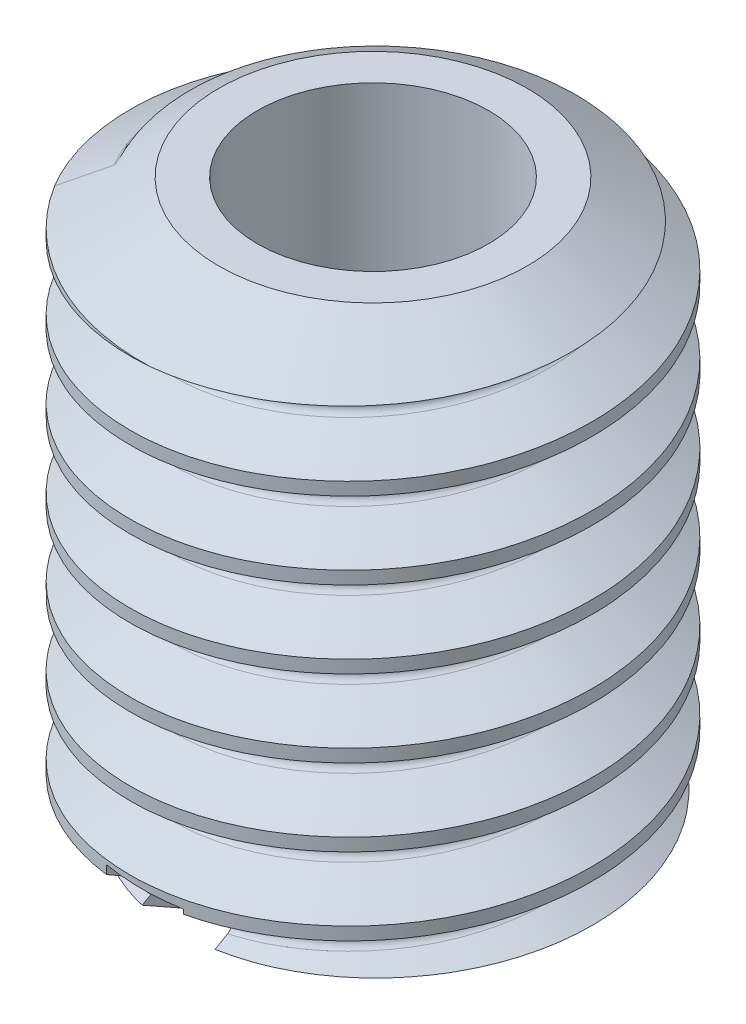
SolidWorks part; units mm, degrees
ref_plane "Front Plane" through (0, 0, 0) normal (0, 0, 1) x (1, 0, 0)
ref_plane "Top Plane" through (0, 0, 0) normal (0, 1, 0) x (1, 0, 0)
ref_plane "Right Plane" through (0, 0, 0) normal (1, 0, 0) x (0, 0, -1)
sketch "Sketch1" plane through (0, 0, 0) normal (0, 1, 0) x (1, 0, 0)
  circle A0 centre (0, 0) radius 3
  dimension "D1" = 6
extrude "Boss-Extrude1" add sketch "Sketch1" along normal blind 7.5
ref_plane "Plane1" through (0, 8.5, 0) normal (0, 1, 0) x (1, 0, 0)
sketch "Sketch2" plane through (0, 8.5, 0) normal (0, 1, 0) x (1, 0, 0)
  circle A0 centre (0, 0) radius 2.675
  dimension "D1" = 5.35
curve "Helix/Spiral1" pitch 1 height 9 radius 2.675 centre (0, 8.5, 0) axis (0, -1, 0) start towards (0, 0, 1)
sketch "Sketch3" plane through (0, 0, 0) normal (1, 0, 0) x (0, 0, -1)
  line L0 (0, 0) -> (0, 8.5) construction
  line L1 (0, 8.5) -> (-2.3865, 8.5) construction
  line L2 (0, 8.5) -> (0, 9.5) construction
  line L3 (0, 9.5) -> (-3, 9.5) construction
  line L4 (-3, 9.5) -> (-3, 8) construction
  line L5 (-2.3865, 8.5625) -> (-2.3865, 8.4375) construction
  line L6 (-2.3865, 8.5) -> (-3.3865, 8.5) construction
  line L7 (-2.3865, 8.5625) -> (-3.2525, 9.0625) construction
  line L8 (-2.3865, 8.4375) -> (-3.2525, 7.9375) construction
  line L9 (-2.4406, 8.5938) -> (-3, 8.9167)
  line L10 (-3, 8.9167) -> (-3, 8.0833)
  line L11 (-3, 8.0833) -> (-2.4406, 8.4062)
  arc A0 (-2.4406, 8.4062) -> (-2.4406, 8.5938) centre (-2.4948, 8.5) ccw
  point P9 (-3, 8.9167)
  point P15 (-3, 8.0833)
  dimension "D1" = 8.5
  dimension "D2" = 2.3865
  dimension "D3" = 1
  dimension "D4" = 3
  dimension "D5" = 1.5
  dimension "D6" = 0.0625
  dimension "D7" = 0.125
  dimension "D8" = 1
  dimension "D9" = 1
  dimension "D10" = 1
  dimension "D11" = 30
  dimension "D12" = 60
sweep "Cut-Sweep1" cut profiles "Sketch3" path "Helix/Spiral1" align with end faces yes
sketch "Sketch4" plane through (0, 0, 0) normal (1, 0, 0) x (0, 0, -1)
  line L0 (-3, 0) -> (0, 0) construction
  line L1 (0, 0) -> (0, 7.5) construction
  line L2 (2.6029, 7.5) -> (-2.0345, 7.5) construction
  line L3 (0, 7.5) -> (-3, 7.5) construction
  line L4 (-3, 7.5) -> (-2, 7.5)
  line L5 (-2, 7.5) -> (-3, 6.9226)
  line L6 (-3, 6.9226) -> (-3, 7.5)
  line L7 (-2, 0) -> (-3, 0)
  line L8 (-3, 0) -> (-3, 0.5774)
  line L9 (-3, 0.5774) -> (-2, 0)
  dimension "D1" = 3
  dimension "D2" = 3
  dimension "D3" = 1
  dimension "D4" = 30
  dimension "D5" = 30
  dimension "D6" = 1
revolve "Cut-Revolve1" cut sketch "Sketch4" angle 360 about L1
sketch "Sketch5" plane through (0, 0, 0) normal (0, 1, 0) x (1, 0, 0)
  circle A0 centre (0, 0) radius 1.5
  dimension "D1" = 3
extrude "Cut-Extrude2" cut sketch "Sketch5" along normal through all
sketch "Sketch6" plane through (0, 0, 0) normal (0, 1, 0) x (1, 0, 0)
  line L1 (0.5, -3) -> (-0.5, -3)
  line L2 (0.5, -3) -> (0.5, 3)
  line L3 (0.5, 3) -> (-0.5, 3)
  line L4 (-0.5, -3) -> (-0.5, 3)
  line L5 (0.5, -3) -> (-0.5, 3) construction
  line L6 (0.5, 3) -> (-0.5, -3) construction
  point P0 (0, 0)
  dimension "D1" = 6
  dimension "D2" = 1
extrude "Cut-Extrude4" cut sketch "Sketch6" along normal blind 1
